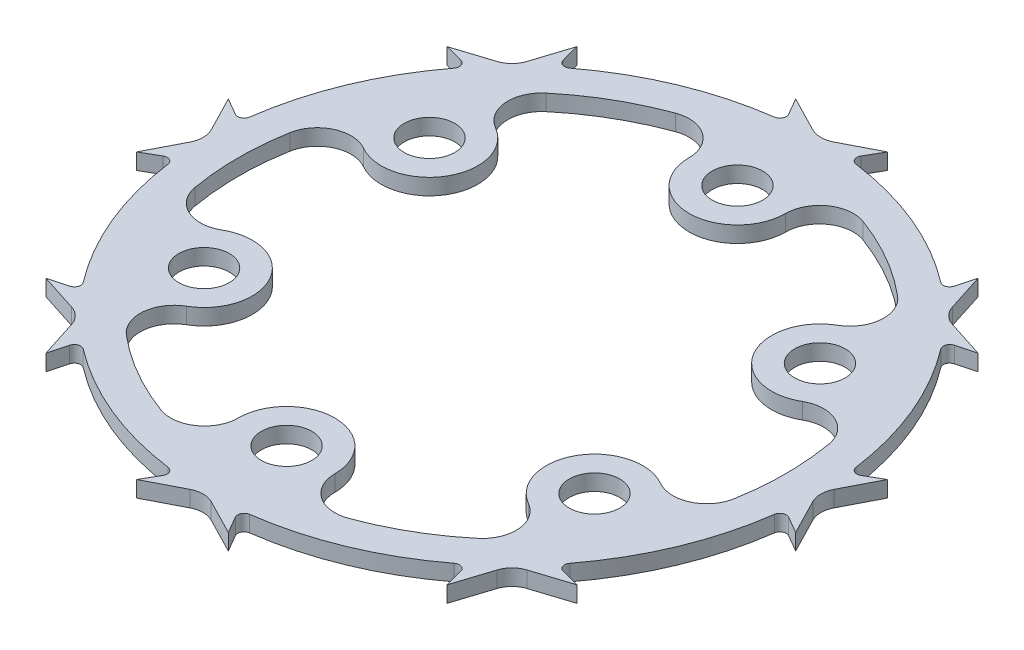
SolidWorks part; units mm, degrees
ref_plane "Front Plane" through (0, 0, 0) normal (0, 0, 1) x (1, 0, 0)
ref_plane "Top Plane" through (0, 0, 0) normal (0, 1, 0) x (1, 0, 0)
ref_plane "Right Plane" through (0, 0, 0) normal (1, 0, 0) x (0, 0, -1)
sketch "Sketch1" plane through (0, 0, 0) normal (0, 1, 0) x (1, 0, 0)
  circle A0 centre (0, 0) radius 26.9875
  circle A1 centre (0, 0) radius 30.1625
  dimension "D1" = 60.325
  dimension "D2" = 3.175
extrude "Boss-Extrude1" add sketch "Sketch1" along normal blind 1.5875
sketch "Sketch2" plane through (0, 1.5875, 0) normal (0, 1, 0) x (1, 0, 0)
  arc A0 (-4.7625, 22.225) -> (4.7625, 22.225) centre (0, 22.225) ccw
  circle A1 centre (0, 0) radius 26.9875 construction
  arc A2 (-4.7625, 22.225) -> (-9.2373, 25.3574) centre (-8.0962, 22.225) ccw
  arc A3 (4.7625, 22.225) -> (9.2373, 25.3574) centre (8.0962, 22.225) cw
  circle A4 centre (0, 22.225) radius 2.4892
  circle M3 centre (0, 0) radius 26.9875
  dimension "D1" = 9.525
  dimension "D4" = 4.9784
extrude "Boss-Extrude2" add sketch "Sketch2" against normal up to surface (1.5875 mm away) contours A0 A3 A2 A4 M3 region at (-6.0653, 1.5875, -25.1264) up to face at (0, 0, 30.1625)
pattern_circular "CirPattern1" count 6 over 360 about axis through (0, 1.5875, 0) along (0, 1, 0) of "Boss-Extrude2"
sketch "Sketch3" plane through (0, 1.5875, 0) normal (0, 1, 0) x (1, 0, 0)
  line L0 (0, 22.225) -> (0, 30.1625) construction
  line L1 (0, 30.1625) -> (3.175, 30.1625) construction
  line L2 (0, 30.1625) -> (-3.175, 30.1625) construction
  line L3 (-3.175, 30.1625) -> (-4.517, 32.4869)
  line L4 (-4.517, 32.4869) -> (0, 30.1625)
  line L5 (3.175, 30.1625) -> (4.517, 32.4869)
  line L6 (4.517, 32.4869) -> (0, 30.1625)
  line L10 (-3.175, 29.9949) -> (0, 30.1625)
  line L11 (3.175, 29.9949) -> (0, 30.1625)
  circle A0 centre (0, 0) radius 30.1625 construction
  arc A1 (-3.175, 30.1625) -> (-3.175, 29.9949) centre (-3.0796, 30.0787) ccw
  arc A2 (3.175, 30.1625) -> (3.175, 29.9949) centre (3.0796, 30.0787) cw
  circle M11 centre (0, 0) radius 30.1625
  dimension "D8" = 0.127
  dimension "D10" = 0.127
  dimension "D1" = 3.175
  dimension "D2" = 3.175
  dimension "D3" = 120
  dimension "D4" = 120
  dimension "D5" = 5.08
  dimension "D6" = 5.08
  dimension "D7" = 3.175
  dimension "D9" = 3.175
extrude "Boss-Extrude3" add sketch "Sketch3" against normal up to surface (1.5875 mm away) contours A2 L5 L6 M11 | L3 A1 L4 M11 region at (-2.5562, 1.5875, -30.8987) region at (2.5562, 1.5875, -30.8987) up to face at (0, 0, 30.1625)
fillet "Fillet1" radius 2.286 1 edges at (0, 0.7937, -30.1625)
fillet "Fillet2" radius 1.524 2 edges at (3.175, 0.7937, -29.9949) (-3.175, 0.7937, -29.9949)
fillet "Fillet3" radius 0.635 2 edges at (-3.175, 0.7937, -30.1625) (3.175, 0.7937, -30.1625)
pattern_circular "CirPattern2" count 8 over 360 about axis through (0, 1.5875, 0) along (0, 1, 0) of "Fillet3", "Fillet2", "Fillet1", "Boss-Extrude3"
